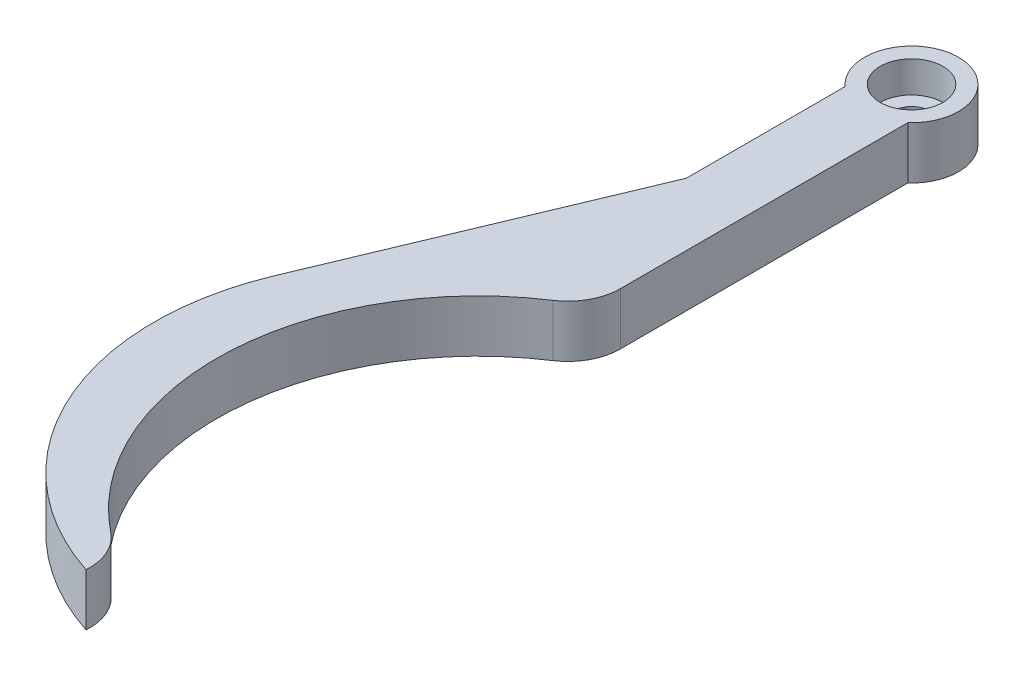
SolidWorks part; units mm, degrees
ref_plane "前视基准面" through (0, 0, 0) normal (0, 0, 1) x (1, 0, 0)
ref_plane "上视基准面" through (0, 0, 0) normal (0, 1, 0) x (1, 0, 0)
ref_plane "右视基准面" through (0, 0, 0) normal (1, 0, 0) x (0, 0, -1)
other "Configuration Table"
sketch "草图3" plane through (0, 0, 0) normal (0, 1, 0) x (1, 0, 0)
  line L0 (0, 0) -> (0, -9.9636) construction
  line L1 (-3, -3.3541) -> (3, -3.3541) construction
  line L2 (-3, -3.3541) -> (-3, -7.4162)
  line L3 (3, -3.3541) -> (3, -7.4162)
  line L7 (3, -7.4162) -> (3, -10.583)
  line L10 (-3, -43.8541) -> (3, -43.8541)
  line L11 (3, -43.8541) -> (3, -10.583)
  line L13 (-3, -7.4162) -> (-3, -43.8541)
  arc A0 (3, -3.3541) -> (-3, -3.3541) centre (0, 0) ccw
  point P6 (0, -3.3541)
  dimension "D1" = 9
  dimension "D2" = 6
  dimension "16.66" = 40.5
extrude "凸台-拉伸2" add sketch "草图3" along normal blind 5
sketch "草图4" plane through (0, 5, 0) normal (0, 1, 0) x (1, 0, 0)
  circle A0 centre (0, 0) radius 1.65
  dimension "D1" = 3.3
extrude "切除-拉伸1" cut sketch "草图4" against normal up to surface (5 mm away) up to face at (0, 0, 21.6406)
sketch "草图6" plane through (0, 5, 0) normal (0, 1, 0) x (1, 0, 0)
  line L0 (14.4495, -55.9701) -> (14.4495, -20.0301) construction
  line L1 (14.4495, -55.9701) -> (3, -43.8541) construction
  line L2 (3, -68.0861) -> (0.6636, -72.1328) construction
  line L3 (3, -43.8541) -> (-3, -43.8541) construction
  line L4 (3, -33.746) -> (-3, -33.746)
  line L5 (3, -43.8541) -> (3, -3.3541) construction
  line L6 (-3, -3.3541) -> (-3, -43.8541) construction
  line L7 (14.4495, -55.9701) -> (1.9495, -77.6207) construction
  line L8 (1.9495, -77.6207) -> (0.7225, -79.746)
  arc A0 (3, -43.8541) -> (3, -68.0861) centre (14.4495, -55.9701) ccw construction
  arc A1 (-3, -43.8541) -> (0.6636, -72.1328) centre (14.4495, -55.9701) ccw construction
  arc A4 (-3, -33.746) -> (0.7225, -79.746) centre (8.4495, -55.9701) ccw
  arc A5 (3, -33.746) -> (1.9495, -77.6207) centre (14.4495, -55.9701) ccw
  dimension "D1" = 33.34
  dimension "D3" = 30
  dimension "D4" = 30
  dimension "D2" = 43.38
extrude "凸台-拉伸3" add sketch "草图6" against normal blind 5
sketch "草图7" plane through (0, 5, 0) normal (0, 1, 0) x (1, 0, 0)
  circle A0 centre (0, 0) radius 3
  dimension "D1" = 6
extrude "切除-拉伸2" cut sketch "草图7" against normal blind 3
sketch "草图8" plane through (0, 5, 0) normal (0, 1, 0) x (1, 0, 0)
  line L0 (-3, -38.0672) -> (-3, -43.8541)
  line L1 (-3, -43.8541) -> (3, -43.8541)
  line L2 (3, -43.8541) -> (3, -33.746)
  line L3 (3, -43.8541) -> (3, -3.3541) construction
  arc A0 (3, -33.746) -> (-3, -38.0672) centre (14.4495, -55.9701) ccw
extrude "切除-拉伸3" cut sketch "草图8" against normal blind 7.5
sketch "草图9" plane through (0, 5, 0) normal (0, 1, 0) x (1, 0, 0)
  line L0 (-3, -18.5501) -> (-14.615, -46.3249)
  line L1 (-3, -3.3541) -> (-3, -33.746) construction
  line L2 (-3, -33.746) -> (-3, -18.5501)
  arc A0 (-3, -33.746) -> (0.7225, -79.746) centre (8.4495, -55.9701) ccw construction
  arc A1 (-3, -33.746) -> (-14.615, -46.3249) centre (8.4495, -55.9701) ccw
extrude "凸台-拉伸4" add sketch "草图9" against normal blind 5
fillet "圆角1" radius 5 2 edges at (1.9495, 2.5, 77.6207) (3, 2.5, 33.746)
